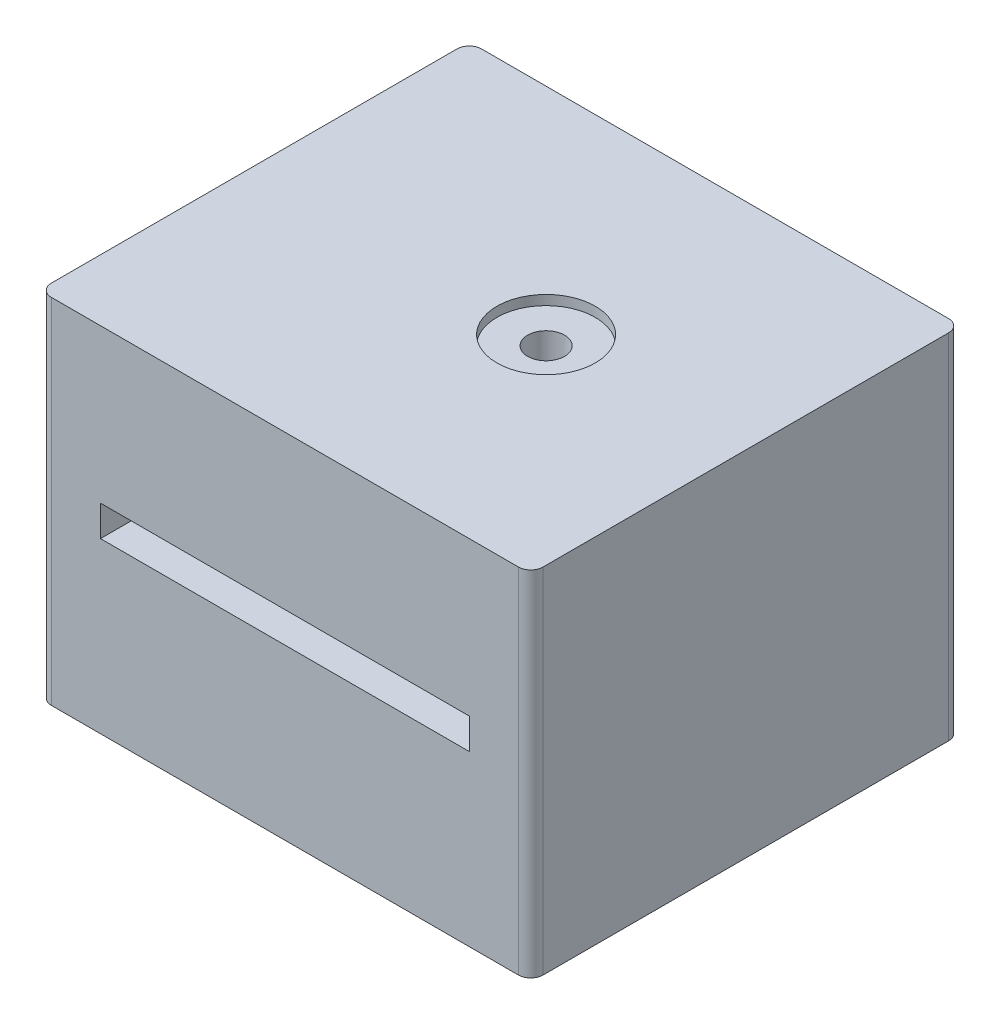
SolidWorks part; units mm, degrees
ref_plane "前视基准面" through (0, 0, 0) normal (0, 0, 1) x (1, 0, 0)
ref_plane "上视基准面" through (0, 0, 0) normal (0, 1, 0) x (1, 0, 0)
ref_plane "右视基准面" through (0, 0, 0) normal (1, 0, 0) x (0, 0, -1)
other "Configuration Table"
sketch "Sketch2" plane through (0, 0, 0) normal (0, 1, 0) x (1, 0, 0)
  line L1 (-80, -70) -> (80, -70)
  line L2 (-80, -70) -> (-80, 70)
  line L3 (-80, 70) -> (80, 70)
  line L4 (80, -70) -> (80, 70)
  point P4 (-80, 0)
  point P6 (0, 70)
  dimension "D1" = 140
  dimension "D2" = 160
extrude "BOX_EXTRUDE" add sketch "Sketch2" along normal blind 100 and the other way blind 15
sketch "Sketch3" plane through (0, 100, 0) normal (0, 1, 0) x (1, 0, 0)
  line L1 (-60, 50) -> (60, 50)
  line L2 (-60, 50) -> (-60, -50)
  line L3 (-60, -50) -> (60, -50)
  line L4 (60, 50) -> (60, -50)
  point P4 (0, 50)
  point P7 (-60, 0)
  dimension "D1" = 120
  dimension "D2" = 100
extrude "BOX_INNER_CUT" cut sketch "Sketch3" against normal blind 40 from offset 20 contours L2 L1 L4 L3 offset against normal yes
sketch "Sketch6" plane through (0, 100, 0) normal (0, 1, 0) x (1, 0, 0)
  line L0 (0, 30.656) -> (0, -17.5007) construction
  circle A0 centre (15, 0) radius 6
  circle A1 centre (-15, 0) radius 6
  dimension "D2" = 12
  dimension "D1" = 15
extrude "SHAFT_CUT" cut sketch "Sketch6" against normal blind 40 from offset 60 offset against normal yes
sketch "Sketch9" plane through (0, 100, 0) normal (0, 1, 0) x (1, 0, 0)
  circle A0 centre (15, 0) radius 8
  circle A2 centre (-15, 0) radius 16
  dimension "D1" = 16
  dimension "D2" = 32
extrude "BEARING_CUTS_INSIDE_BOX" cut sketch "Sketch9" against normal blind 10 from offset 60 offset against normal yes
sketch "Sketch11" plane through (0, 0, 70) normal (0, 0, 1) x (1, 0, 0)
  line L0 (-80, -15) -> (80, -15) construction
  line L1 (-60, 50) -> (60, 50)
  line L2 (-60, 50) -> (-60, 40)
  line L3 (-60, 40) -> (60, 40)
  line L4 (60, 50) -> (60, 40)
  point P4 (0, 50)
  dimension "D1" = 120
  dimension "D2" = 10
  dimension "D3" = 55
extrude "SCISSOR_CUT" cut sketch "Sketch11" against normal blind 20
sketch "Sketch12" plane through (0, 100, 0) normal (0, 1, 0) x (1, 0, 0)
  circle A0 centre (15, 0) radius 16
  dimension "D1" = 32
extrude "MOTOR_HOLE_CUT" cut sketch "Sketch12" against normal blind 3.15
sketch "Sketch15" plane through (0, 96.85, 0) normal (0, 1, 0) x (1, 0, 0)
  circle A0 centre (15, 0) radius 6
  dimension "D1" = 12
extrude "RIGHT_SHAFT_LID_CUT" cut sketch "Sketch15" against normal up to next
sketch "Sketch18" plane through (0, 100, 0) normal (0, 1, 0) x (1, 0, 0)
  circle A0 centre (-15, 0) radius 8
  dimension "D1" = 16
extrude "LEFT_BEARING_LID_CUT" cut sketch "Sketch18" against normal blind 10 from offset 10 offset against normal yes
fillet "OUTER_EDGES_FILLET" radius 4 4 edges at (-80, 42.5, -70) (80, 42.5, -70) (80, 42.5, 70) (-80, 42.5, 70)
